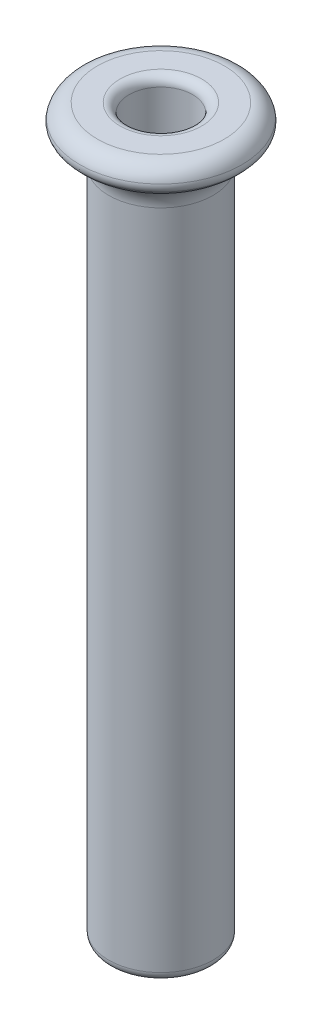
SolidWorks part; units mm, degrees
ref_plane "Front Plane" through (0, 0, 0) normal (0, 0, 1) x (1, 0, 0)
ref_plane "Top Plane" through (0, 0, 0) normal (0, 1, 0) x (1, 0, 0)
ref_plane "Right Plane" through (0, 0, 0) normal (1, 0, 0) x (0, 0, -1)
sketch "Sketch1" plane through (0, 0, 0) normal (0, 0, 1) x (1, 0, 0)
  line L0 (0, 0) -> (0, -12.846) construction
  line L1 (2.6, 0) -> (9, 0)
  line L2 (9, 0) -> (9, -3)
  line L3 (9, -3) -> (5.75, -3)
  line L4 (5.75, -3) -> (5.75, -80)
  line L5 (5.75, -80) -> (2.6, -80)
  line L6 (2.6, -80) -> (2.6, 0)
  line L7 (0, -8) -> (2.6, -8)
  line L9 (0, 0) -> (3.5, 0)
  line L10 (0, 0) -> (0, -8)
  line L11 (0, -8) -> (3.5, -8)
  line L12 (3.5, 0) -> (3.5, -8)
  dimension "D1" = 3.25
  dimension "D2" = 6.4
  dimension "D3" = 80
  dimension "D4" = 3
  dimension "D5" = 2.6
  dimension "D6" = 3.5
  dimension "D7" = 8
revolve "Revolve1" add sketch "Sketch1" angle 360 about L0 region at (4.3294, -39.5436, 0)
fillet "Fillet1" radius 3 1 edges at (-5.75, -3, 0) type face fillet first side face at (-5.75, -3, 0) second side face at (-5.75, -80, 0)
fillet "Fillet3" radius 2 1 edges at (-9, 0, 0)
fillet "Fillet4" radius 1 1 edges at (-3.5, 0, 0)
fillet "Fillet7" radius 0.5 1 edges at (-2.6, -8, 0) type face fillet first side face at (-3.5, -8, 0) second side face at (-2.6, -8, 0)
fillet "Fillet9" radius 1 1 edges at (-2.6, -80, 0) type face fillet first side face at (-2.6, -80, 0) second side face at (-2.6, -8.5, 0)
fillet "Fillet10" radius 1 1 edges at (-5.75, -80, 0) type face fillet first side face at (3.6, -80, 0) second side face at (5.75, -6, 0)
fillet "Fillet11" radius 3 1 edges at (-9, -3, 0)
fillet "Fillet12" radius 1 1 edges at (-9, -2, 0)
fillet "Fillet13" radius 1 1 edges at (-3.5, -8, 0)
